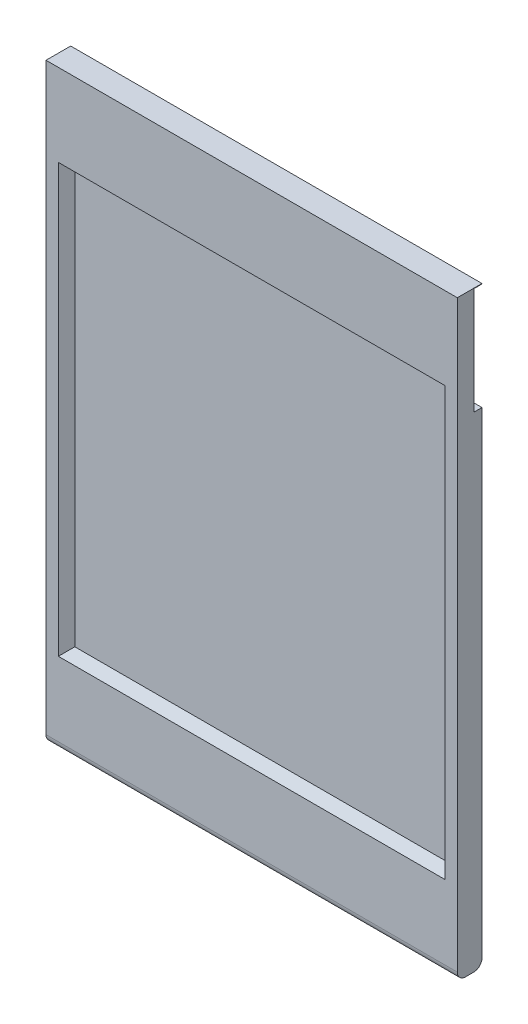
SolidWorks part; units mm, degrees
ref_plane "Alzado" through (0, 0, 0) normal (0, 0, 1) x (1, 0, 0)
ref_plane "Planta" through (0, 0, 0) normal (0, 1, 0) x (1, 0, 0)
ref_plane "Vista lateral" through (0, 0, 0) normal (1, 0, 0) x (0, 0, -1)
sketch "Croquis1" plane through (0, 0, 0) normal (0, 0, 1) x (1, 0, 0)
  line L1 (250, -360) -> (-250, -360)
  line L2 (250, -360) -> (250, 360)
  line L3 (250, 360) -> (-250, 360)
  line L4 (-250, -360) -> (-250, 360)
  line L5 (250, -360) -> (-250, 360) construction
  line L6 (250, 360) -> (-250, -360) construction
  point P0 (0, 0)
  dimension "D1" = 720
  dimension "D2" = 500
extrude "Saliente-Extruir1" add sketch "Croquis1" along normal blind 30
sketch "Croquis2" plane through (0, 0, 30) normal (0, 0, 1) x (1, 0, 0)
  line L1 (225, -250) -> (-225, -250)
  line L2 (225, -250) -> (225, 250)
  line L3 (225, 250) -> (-225, 250)
  line L4 (-225, -250) -> (-225, 250)
  line L5 (225, -250) -> (-225, 250) construction
  line L6 (225, 250) -> (-225, -250) construction
  point P0 (0, 0)
  dimension "D1" = 500
  dimension "D2" = 450
extrude "Cortar-Extruir1" cut sketch "Croquis2" against normal blind 10
chamfer "Chaflán1" distance 10 angle 45 1 edges at (0, 250, 30)
chamfer "Chaflán2" distance 10 angle 45 3 edges at (225, 5, 30) (0, -250, 30) (-225, 5, 30)
fillet "Redondeo2" radius 10 1 edges at (0, -360, 30)
fillet "Redondeo3" radius 10 1 edges at (0, -360, 0)
sketch "Croquis11" plane through (0, 0, 0) normal (0, 0, -1) x (-1, 0, 0)
  line L0 (250, 360) -> (250, -350) construction
  line L1 (-250, 310) -> (230, 310)
  line L2 (-250, 310) -> (-250, 290)
  line L3 (-250, 290) -> (230, 290)
  line L4 (230, 310) -> (230, 290)
  line L5 (-250, 310) -> (230, 290) construction
  line L6 (-250, 290) -> (230, 310) construction
  line L7 (-250, 360) -> (250, 360) construction
  point P0 (-10, 300)
  dimension "D1" = 20
  dimension "D2" = 480
  dimension "D3" = 50
  dimension "D4" = 20
extrude "Cortar-Extruir5" cut sketch "Croquis11" against normal blind 7
sketch "Croquis12" plane through (250, 0, 0) normal (1, 0, 0) x (0, 0, -1)
  line L0 (0, -350) -> (0, 290) construction
  line L1 (-10, 359.4292) -> (0, 359.4292)
  line L2 (-10, 359.4292) -> (-10, 229.4292)
  line L3 (-10, 229.4292) -> (0, 229.4292)
  line L4 (0, 359.4292) -> (0, 229.4292)
  line L5 (-10, 359.4292) -> (0, 229.4292) construction
  line L6 (-10, 229.4292) -> (0, 359.4292) construction
  point P0 (-5, 294.4292)
  dimension "D1" = 130
  dimension "D2" = 10
extrude "Cortar-Extruir6" cut sketch "Croquis12" against normal blind 20
